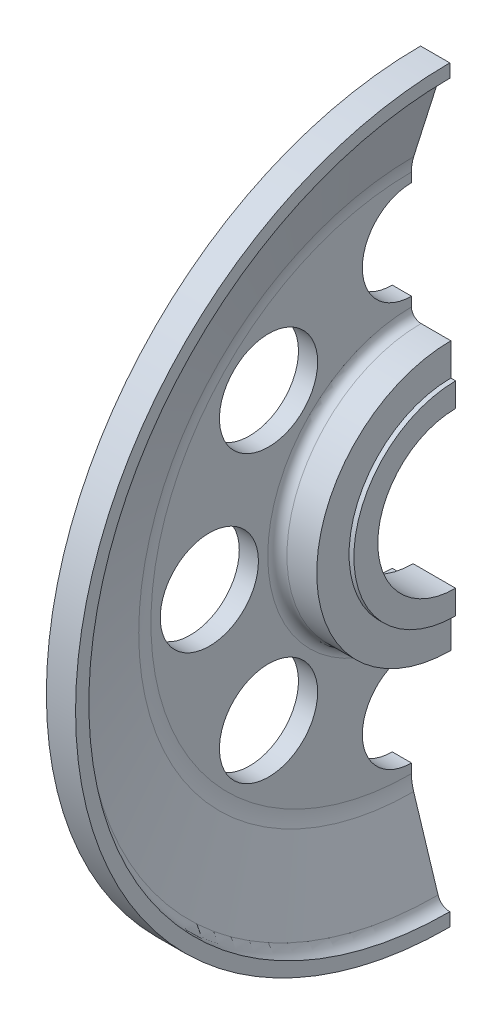
SolidWorks part; units mm, degrees
ref_plane "Piano frontale" through (0, 0, 0) normal (0, 0, 1) x (1, 0, 0)
ref_plane "Piano superiore" through (0, 0, 0) normal (0, 1, 0) x (1, 0, 0)
ref_plane "Piano destro" through (0, 0, 0) normal (1, 0, 0) x (0, 0, -1)
sketch "Sketch1" plane through (0, 0, 0) normal (0, 0, 1) x (1, 0, 0)
  line L0 (-62.2549, -192.8871) -> (72.6149, -192.8871) construction
  line L1 (0, -192.8871) -> (0, 154.8776) construction
  line L2 (35.3511, 156.8497) -> (0, 44.7302) construction
  line L3 (14.3058, 90.1023) -> (23.6104, 119.6129)
  line L4 (23.6104, 119.6129) -> (48, 119.6129)
  line L5 (38.2212, 101.3202) -> (17.8513, 36.7152)
  line L6 (16, 24.687) -> (16, -72.8871)
  line L7 (24, -80.8871) -> (48.9, -80.8871)
  line L8 (48.9, -80.8871) -> (48.9, -115.8871)
  line L9 (48.9, -115.8871) -> (0, -115.8871)
  line L10 (48, 119.6129) -> (48, 108.4903)
  line L11 (0, 79.6129) -> (0, -115.8871)
  circle A0 centre (0, 94.6129) radius 15 construction
  arc A1 (0, 79.6129) -> (14.3058, 90.1023) centre (0, 94.6129) ccw
  arc A3 (48, 108.4903) -> (38.2212, 101.3202) centre (48, 98.237) ccw
  arc A4 (16, -72.8871) -> (24, -80.8871) centre (24, -72.8871) ccw
  arc A5 (16, 24.687) -> (17.8513, 36.7152) centre (56, 24.687) cw
  dimension "D2" = 17.5
  dimension "D3" = 48
  dimension "D4" = 40
  dimension "D5" = 272.5
  dimension "D1" = 30
  dimension "D8" = 8
  dimension "D9" = 40
  dimension "D6" = 77
  dimension "D7" = 16
  dimension "D10" = 35
  dimension "D11" = 48.9
revolve "Puleggia" add sketch "Sketch1" angle 360 about L0
ref_axis "Axis1" through (48.9, -192.8871, 0) along (-1, 0, 0)
mirror "Mirror" about plane through (0, 79.6129, 0) normal (1, 0, 0) of "Puleggia"
sketch "Sketch2" plane through (0, 0, 0) normal (1, 0, 0) x (0, 0, -1)
  line L0 (0, -192.6685) -> (0, -72.8871) construction
  line L1 (0, -72.8871) -> (0, -24.1001) construction
  line L3 (0, -24.1001) -> (0, 24.687) construction
  circle A0 centre (0, -24.1001) radius 41
  circle A1 centre (0, -192.8871) radius 120 construction
  circle A2 centre (0, -192.8871) radius 217.5741 construction
  dimension "D2" = 82
extrude "Foro" cut sketch "Sketch2" against normal blind 120 from offset 60
pattern_circular "PatternFori" count 8 over 360 about axis through (48.9, -192.8871, 0) along (-1, 0, 0) of "Foro"
sketch "Sketch3" plane through (0, 0, 0) normal (0, 0, 1) x (1, 0, 0)
  line L0 (48.9, -115.8871) -> (48.9, -107.8871)
  line L1 (48.9, -107.8871) -> (52.9, -107.8871)
  line L2 (52.9, -107.8871) -> (52.9, -127.8871)
  line L3 (52.9, -127.8871) -> (48.2033, -127.8871)
  line L4 (48.2033, -127.8871) -> (17.4, -127.8871)
  line L5 (17.4, -127.8871) -> (17.4, -115.8871)
  line L6 (17.4, -115.8871) -> (48.9, -115.8871)
  dimension "D1" = 4
  dimension "D2" = 31.5
  dimension "D3" = 12
  dimension "D4" = 8
revolve "Revolve1" add sketch "Sketch3" angle 360 about axis through (48.9, -192.8871, 0) along (-1, 0, 0)
mirror "Mirror1" about plane through (0, 0, 0) normal (1, 0, 0) of "Revolve1"
sketch "Sketch4" plane through (0, 0, 0) normal (0, 0, 1) x (1, 0, 0)
  line L0 (0, -192.8871) -> (0, 154.8776) construction
  line L1 (0, 235.3441) -> (-165.9416, 235.3441)
  line L2 (0, 235.3441) -> (0, -649.4742)
  line L3 (0, -649.4742) -> (-165.9416, -649.4742)
  line L4 (-165.9416, 235.3441) -> (-165.9416, -649.4742)
extrude "Cut-Extrude1" cut sketch "Sketch4" against normal through all both and the other way through all
sketch "Sketch5" plane through (0, 0, 0) normal (0, 1, 0) x (1, 0, 0)
  line L1 (214.9104, 0) -> (-183.7353, 0)
  line L2 (214.9104, 0) -> (214.9104, 571.6596)
  line L3 (214.9104, 571.6596) -> (-183.7353, 571.6596)
  line L4 (-183.7353, 0) -> (-183.7353, 571.6596)
extrude "Cut-Extrude2" cut sketch "Sketch5" against normal through all both and the other way through all
sketch "Sketch6" plane through (0, 0, 0) normal (1, 0, 0) x (0, 0, -1)
  line L0 (154.8116, -192.8871) -> (-547.4317, -192.8871)
split line "Split Line1"
